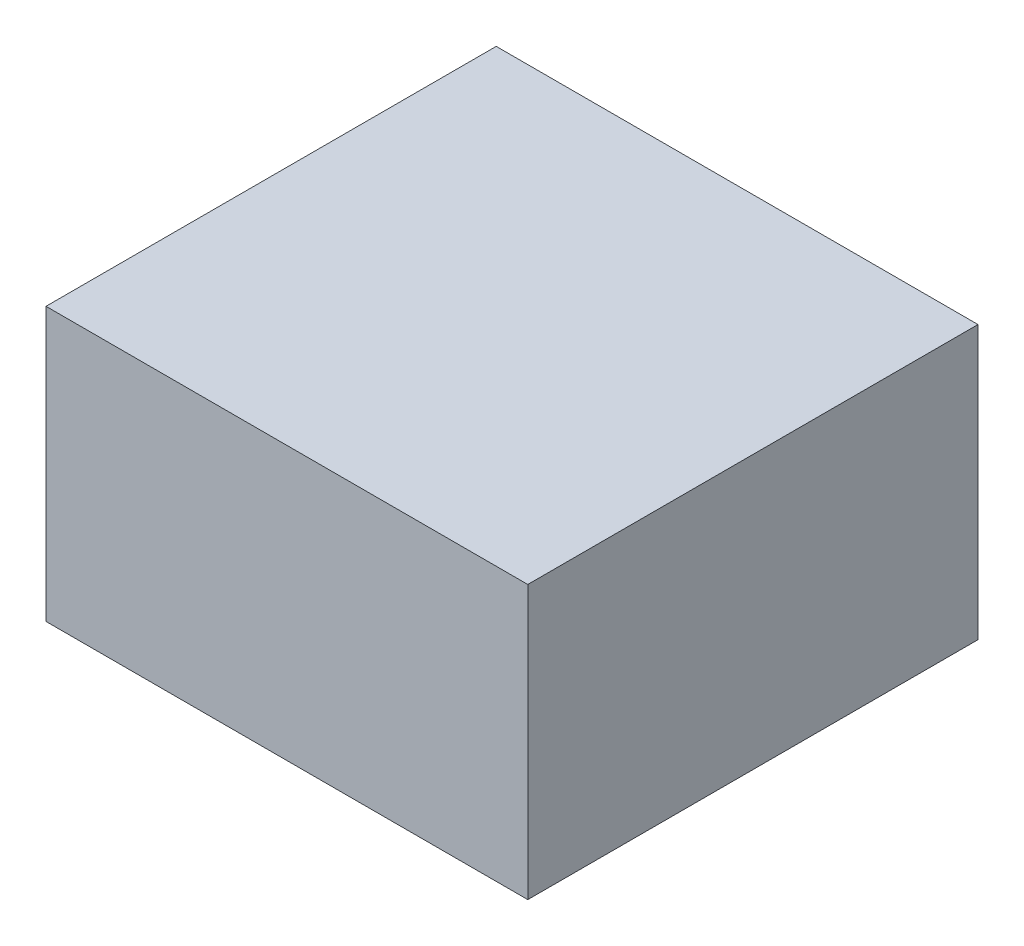
SolidWorks part; units mm, degrees
ref_plane "前视基准面" through (0, 0, 0) normal (0, 0, 1) x (1, 0, 0)
ref_plane "上视基准面" through (0, 0, 0) normal (0, 1, 0) x (1, 0, 0)
ref_plane "右视基准面" through (0, 0, 0) normal (1, 0, 0) x (0, 0, -1)
other "Configuration Table"
sketch "草图1" plane through (0, 0, 0) normal (0, 0, 1) x (1, 0, 0)
  line L1 (-42.8047, 24.2513) -> (42.8047, 24.2513)
  line L2 (-42.8047, 24.2513) -> (-42.8047, -24.2513)
  line L3 (-42.8047, -24.2513) -> (42.8047, -24.2513)
  line L4 (42.8047, 24.2513) -> (42.8047, -24.2513)
  line L5 (-42.8047, 24.2513) -> (42.8047, -24.2513) construction
  line L6 (-42.8047, -24.2513) -> (42.8047, 24.2513) construction
  point P0 (0, 0)
extrude "凸台-拉伸1" add sketch "草图1" along normal blind 80
sketch3d "3D草图1"
  line L0 (-42.8047, 24.2513, 80) -> (42.8047, -24.2513, 80)
  line L1 (42.8047, -24.2513, 80) -> (42.8047, 24.2513, 0)
  line L2 (42.8047, 24.2513, 0) -> (-42.8047, 24.2513, 80)
  line L3 (-42.8047, 24.2513, 80) -> (-42.8047, -24.2513, 0)
  line L4 (-42.8047, -24.2513, 0) -> (42.8047, 24.2513, 0)
  line L5 (-42.8047, -24.2513, 0) -> (42.8047, -24.2513, 80)
